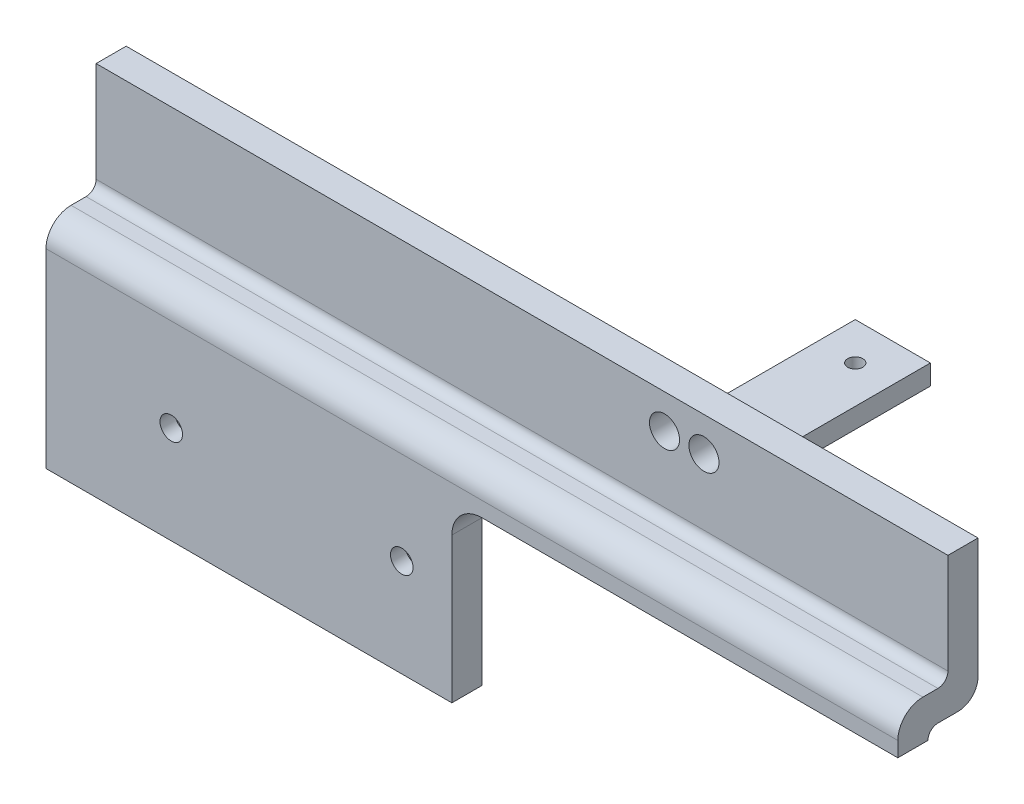
SolidWorks part; units mm, degrees
material "ABS"
ref_plane "Piano frontale" through (0, 0, 0) normal (0, 0, 1) x (1, 0, 0)
ref_plane "Piano superiore" through (0, 0, 0) normal (0, 1, 0) x (1, 0, 0)
ref_plane "Piano destro" through (0, 0, 0) normal (1, 0, 0) x (0, 0, -1)
sketch "Schizzo1" plane through (0, 0, 0) normal (1, 0, 0) x (0, 0, -1)
  line L0 (0, 0) -> (6, 0)
  line L1 (6, 0) -> (6, 35)
  line L2 (8, 37) -> (12, 37)
  line L3 (16, 41) -> (16, 65)
  line L4 (16, 65) -> (10, 65)
  line L5 (10, 65) -> (10, 45)
  line L6 (8, 43) -> (5, 43)
  line L7 (0, 38) -> (0, 0)
  arc A0 (5, 43) -> (0, 38) centre (5, 38) ccw
  arc A1 (10, 45) -> (8, 43) centre (8, 45) cw
  arc A2 (8, 37) -> (6, 35) centre (8, 35) ccw
  arc A3 (12, 37) -> (16, 41) centre (12, 41) ccw
  dimension "D7" = 5
  dimension "D8" = 2
  dimension "D9" = 4
  dimension "D1" = 37
  dimension "D2" = 43
  dimension "D3" = 6
  dimension "D4" = 16
  dimension "D5" = 6
  dimension "D6" = 28
extrude "Estrusione-Estrusione1" add sketch "Schizzo1" along normal blind 170
sketch "Schizzo2" plane through (0, 0, -6) normal (0, 0, -1) x (-1, 0, 0)
  line L0 (-71, 19.5) -> (-25, 19.5) construction
  line L2 (0, 0) -> (0, 35) construction
  point P0 (-25, 19.5)
  point P2 (-71, 19.5)
  dimension "D1" = 46
  dimension "D2" = 25
  dimension "D3" = 23.5
hole_wizard "Foro lamato per Bullone M5 a testa esagonale-1" positions "Schizzo2" profile "Schizzo3" counterbore size "M5" standard "ISO"
sketch "Schizzo3" plane through (25, 19.5, -6) normal (1, 0, 0) x (0, 1, 0)
  line L0 (0, 0) -> (0, 31.3519)
  line L1 (0, 31.3519) -> (2.25, 30)
  line L2 (2.25, 30) -> (2.25, 3)
  line L3 (2.25, 3) -> (5, 3)
  line L4 (5, 3) -> (5, 0)
  line L5 (5, 0) -> (0, 0)
  line L10 (0, 31.3519) -> (-2.25, 30) construction
  line L11 (0, -6.35) -> (0, 107.95) construction
  dimension "Hole Dia." = 4.5
  dimension "Hole Depth" = 30
  dimension "C'Bore Dia." = 10
  dimension "C'Bore Depth" = 3
  dimension "Drill Angle" = 118
sketch "Schizzo4" plane through (0, 0, -6) normal (0, 0, -1) x (-1, 0, 0)
  line L1 (-170, 0) -> (-81, 0)
  line L2 (-170, 0) -> (-170, 35)
  line L3 (-170, 35) -> (-81, 35)
  line L4 (-81, 0) -> (-81, 35)
  circle A0 centre (-71, 19.5) radius 2.25 construction
  dimension "D1" = 10
  dimension "D2" = 35
extrude "Taglio-Estrusione1" cut sketch "Schizzo4" against normal blind 170
fillet "Raccordo1" radius 6 1 edges at (81, 35, -3)
sketch "Schizzo5" plane through (0, 0, -16) normal (0, 0, -1) x (-1, 0, 0)
  line L1 (-110, 55) -> (-125, 55)
  line L2 (-110, 55) -> (-110, 51)
  line L3 (-110, 51) -> (-125, 51)
  line L4 (-125, 55) -> (-125, 51)
  line L5 (-170, 65) -> (0, 65) construction
  line L6 (-170, 41) -> (-170, 65) construction
  dimension "D1" = 15
  dimension "D2" = 45
  dimension "D3" = 4
  dimension "D4" = 10
extrude "Estrusione-Estrusione2" add sketch "Schizzo5" along normal blind 35.5
sketch "Schizzo6" plane through (0, 55, 0) normal (0, 1, 0) x (1, 0, 0)
  line L1 (110, 16) -> (125, 16) construction
  line L2 (117.5, 16) -> (117.5, 44) construction
  circle A0 centre (117.5, 44) radius 1.5
  dimension "D1" = 3
  dimension "D2" = 28
extrude "Taglio-Estrusione2" cut sketch "Schizzo6" against normal blind 32
sketch "Schizzo7" plane through (0, 0, -16) normal (0, 0, -1) x (-1, 0, 0)
  circle A0 centre (-121.31, 58.175) radius 3
  circle A1 centre (-113.436, 58.175) radius 3
  dimension "D1" = 6
extrude "Taglio-Estrusione3" cut sketch "Schizzo7" against normal blind 10
chamfer "Smusso1" distance 10 angle 45 1 edges at (117.5, 51, -16)
chamfer "Smusso2" distance 2 angle 45 2 edges at (110, 48, -16) (125, 48, -16)
